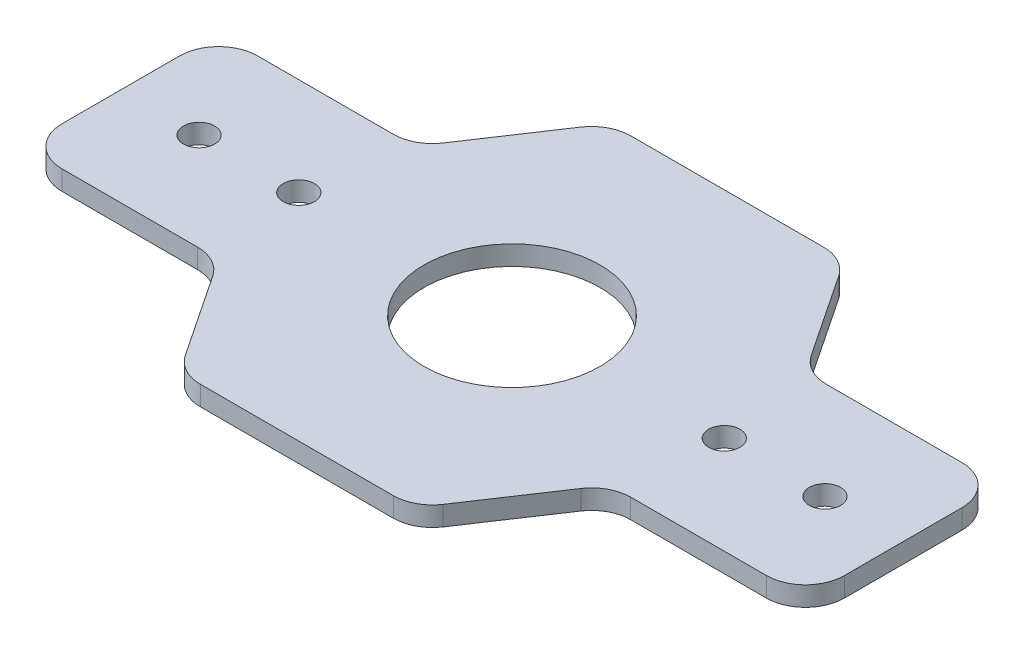
SolidWorks part; units mm, degrees
ref_plane "Front Plane" through (0, 0, 0) normal (0, 0, 1) x (1, 0, 0)
ref_plane "Top Plane" through (0, 0, 0) normal (0, 1, 0) x (1, 0, 0)
ref_plane "Right Plane" through (0, 0, 0) normal (1, 0, 0) x (0, 0, -1)
sketch "Sketch1" plane through (0, 0, 0) normal (0, 1, 0) x (1, 0, 0)
  line L0 (16.2686, 0) -> (85.3314, 0) construction
  line L1 (50.8, 0) -> (50.8, 3.1391) construction
  line L2 (19.05, 15.875) -> (31.75, 34.925)
  line L3 (-12.7, 15.875) -> (19.05, 15.875)
  line L4 (-12.7, 15.875) -> (-12.7, -15.875)
  line L5 (-12.7, -15.875) -> (19.05, -15.875)
  line L6 (114.3, 15.875) -> (114.3, -15.875)
  line L7 (-12.7, 15.875) -> (114.3, -15.875) construction
  line L8 (-12.7, -15.875) -> (114.3, 15.875) construction
  line L9 (31.75, 34.925) -> (69.85, 34.925)
  line L10 (69.85, 34.925) -> (82.55, 15.875)
  line L11 (50.8, 34.925) -> (50.8, 29.0511) construction
  line L12 (69.85, -34.925) -> (82.55, -15.875)
  line L13 (31.75, -34.925) -> (69.85, -34.925)
  line L14 (19.05, -15.875) -> (31.75, -34.925)
  line L15 (82.55, -15.875) -> (114.3, -15.875)
  line L16 (82.55, 15.875) -> (114.3, 15.875)
  circle A0 centre (0, 0) radius 2.54
  circle A1 centre (101.6, 0) radius 2.54
  circle A2 centre (16.2686, 0) radius 2.54 construction
  circle A3 centre (85.3314, 0) radius 2.54 construction
  dimension "D1" = 5.08
  dimension "D3" = 127
  dimension "D4" = 31.75
  dimension "D5" = 69.0628
  dimension "D2" = 101.6
  dimension "D6" = 19.05
  dimension "D7" = 31.75
  dimension "D8" = 38.1
extrude "Boss-Extrude1" add sketch "Sketch1" along normal blind 3.175
fillet "Fillet1" radius 6.35 12 edges at (19.05, 1.5875, -15.875) (31.75, 1.5875, -34.925) (69.85, 1.5875, -34.925) (82.55, 1.5875, -15.875) (114.3, 1.5875, -15.875) (114.3, 1.5875, 15.875) (82.55, 1.5875, 15.875) (69.85, 1.5875, 34.925) (31.75, 1.5875, 34.925) (19.05, 1.5875, 15.875) (-12.7, 1.5875, -15.875) (-12.7, 1.5875, 15.875)
sketch "Sketch2" plane through (0, 3.175, 0) normal (0, 1, 0) x (1, 0, 0)
  circle A0 centre (50.8, 0) radius 14.2875
  circle A1 centre (0, 0) radius 2.54 construction
  dimension "D1" = 50.8
  dimension "D2" = 28.575
extrude "Cut-Extrude1" cut sketch "Sketch2" against normal blind 3.175
sketch "Sketch3" plane through (0, 3.175, 0) normal (0, 1, 0) x (1, 0, 0)
  circle A2 centre (85.2557, 0) radius 2.54
  circle A3 centre (16.1929, 0) radius 2.54
  circle A4 centre (101.6, 0) radius 2.54 construction
  dimension "D1" = 69.0628
  dimension "D2" = 5.08
  dimension "D3" = 5.08
  dimension "D4" = 16.3443
extrude "Cut-Extrude2" cut sketch "Sketch3" against normal through all
sketch "Sketch4"
